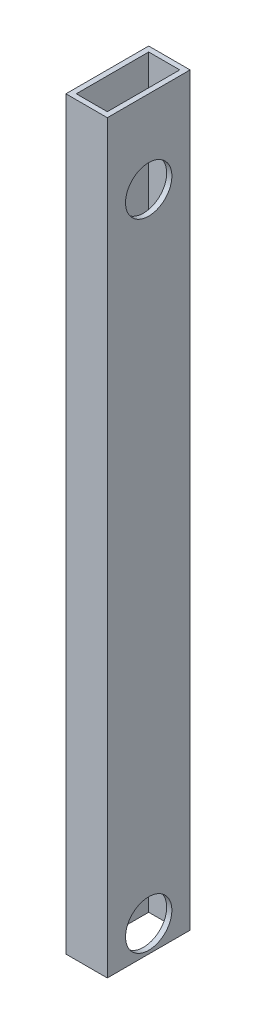
SolidWorks part; units mm, degrees
ref_plane "Front Plane" through (0, 0, 0) normal (0, 0, 1) x (1, 0, 0)
ref_plane "Top Plane" through (0, 0, 0) normal (0, 1, 0) x (1, 0, 0)
ref_plane "Right Plane" through (0, 0, 0) normal (1, 0, 0) x (0, 0, -1)
sketch "Sketch2" plane through (0, 0, 0) normal (0, 1, 0) x (1, 0, 0)
  line L1 (0, 0) -> (25.4, 0)
  line L2 (0, 0) -> (0, 50.8)
  line L3 (0, 50.8) -> (25.4, 50.8)
  line L4 (25.4, 0) -> (25.4, 50.8)
  dimension "D1" = 50.8
  dimension "D2" = 25.4
extrude "Extrude-Thin1" add sketch "Sketch2" along normal blind 457.2 thin thin type one direction reverse wall 3.175
sketch "Sketch3" plane through (25.4, 0, 0) normal (1, 0, 0) x (0, 0, -1)
  line L0 (0, 457.2) -> (0, 0) construction
  line L1 (0, 0) -> (50.8, 0) construction
  line L2 (0, 457.2) -> (50.8, 457.2) construction
  circle A0 centre (25.4, 16.256) radius 14.224
  circle A1 centre (25.4, 406.4) radius 14.224
  dimension "D1" = 28.448
  dimension "D4" = 28.448
  dimension "D5" = 50.8
  dimension "D2" = 25.4
  dimension "D3" = 16.256
  dimension "D6" = 25.4
extrude "Cut-Extrude1" cut sketch "Sketch3" against normal through all
